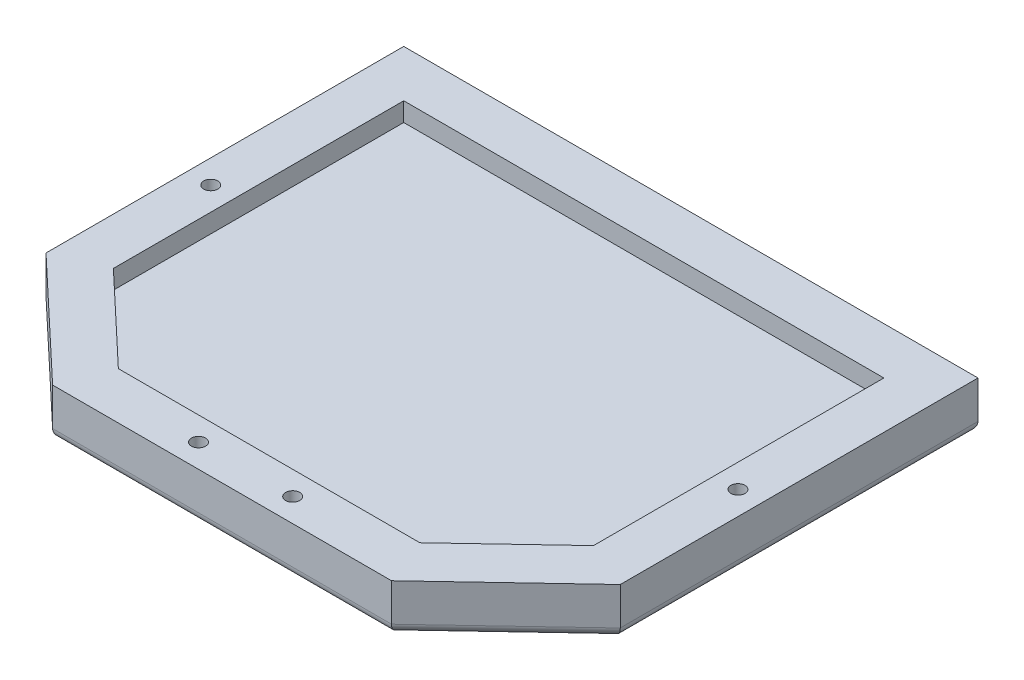
SolidWorks part; units mm, degrees
ref_plane "Płaszczyzna przednia" through (0, 0, 0) normal (0, 0, 1) x (1, 0, 0)
ref_plane "Płaszczyzna górna" through (0, 0, 0) normal (0, 1, 0) x (1, 0, 0)
ref_plane "Płaszczyzna prawa" through (0, 0, 0) normal (1, 0, 0) x (0, 0, -1)
sketch "Szkic1" plane through (0, 0, 0) normal (0, 1, 0) x (1, 0, 0)
  line L0 (-24.7421, -43.1447) -> (36.2579, -43.1447)
  line L1 (36.2579, -43.1447) -> (36.2579, -81.1447)
  line L2 (36.2579, -81.1447) -> (23.7579, -92.9447)
  line L3 (23.7579, -92.9447) -> (-12.2421, -92.9447)
  line L4 (-24.7421, -43.1447) -> (-24.7421, -81.1447)
  line L5 (-24.7421, -81.1447) -> (-12.2421, -92.9447)
  dimension "D1" = 61
  dimension "D2" = 38
  dimension "D3" = 11.8
  dimension "D4" = 12.5
  dimension "D5" = 36
  dimension "D6" = 38
  dimension "D7" = 11.8
extrude "Dodanie-wyciągnięcie1" add sketch "Szkic1" along normal blind 3
sketch "Szkic2" plane through (0, 3, 0) normal (0, 1, 0) x (1, 0, 0)
  line L0 (-19.7421, -48.1447) -> (31.2579, -48.1447)
  line L1 (36.2579, -43.1447) -> (-24.7421, -43.1447) construction
  line L2 (36.2579, -81.1447) -> (36.2579, -43.1447) construction
  line L3 (-19.7421, -48.1447) -> (-19.7421, -78.9888)
  line L7 (31.2579, -48.1447) -> (31.2579, -78.9888)
  line L9 (-19.7421, -78.9888) -> (-10.2549, -87.9447)
  line L10 (-24.7421, -81.1447) -> (-12.2421, -92.9447) construction
  line L11 (-10.2549, -87.9447) -> (21.7707, -87.9447)
  line L12 (-12.2421, -92.9447) -> (23.7579, -92.9447) construction
  line L13 (31.2579, -78.9888) -> (21.7707, -87.9447)
  line L15 (23.7579, -92.9447) -> (36.2579, -81.1447) construction
  dimension "D1" = 51
  dimension "D2" = 5
  dimension "D3" = 5
  dimension "D4" = 5
  dimension "D5" = 5
  dimension "D6" = 5
  dimension "D8" = 5
extrude "Wyciągnięcie-cienka ścianka2" add sketch "Szkic2" along normal blind 2 thin thin type one direction wall 5
sketch "Szkic3" plane through (0, 5, 0) normal (0, 1, 0) x (1, 0, 0)
  line L0 (-12.2421, -92.9447) -> (23.7579, -92.9447) construction
  line L1 (-24.7421, -43.1447) -> (-24.7421, -81.1447) construction
  line L2 (36.2579, -81.1447) -> (36.2579, -43.1447) construction
  circle A0 centre (0.7579, -90.4447) radius 0.75
  circle A1 centre (10.7579, -90.4447) radius 0.75
  circle A2 centre (-22.2421, -66.1447) radius 0.75
  circle A3 centre (33.7579, -66.1447) radius 0.75
  point P15 (0, 0)
  point P17 (0, 0)
  dimension "D3" = 1.5
  dimension "D4" = 1.5
  dimension "D9" = 1.5
  dimension "D10" = 1.5
  dimension "D1" = 10
  dimension "D2" = 13
  dimension "D5" = 2.5
  dimension "D6" = 2.5
  dimension "D7" = 2.5
  dimension "D8" = 2.5
  dimension "D11" = 15
  dimension "D12" = 15
extrude "Wytnij-wyciągnięcie1" cut sketch "Szkic3" against normal blind 40 and the other way blind 27
fillet "Zaokrąglenie2" radius 1 10 edges at (-18.4921, 0, 87.0447) (5.7579, 0, 92.9447) (30.0079, 0, 87.0447) (36.2579, 0, 62.1447) (5.7579, 0, 43.1447) (-24.7421, 0, 62.1447) (0.7579, 0, 89.6947) (10.7579, 0, 89.6947) (-22.2421, 0, 65.3947) (33.7579, 0, 65.3947)
